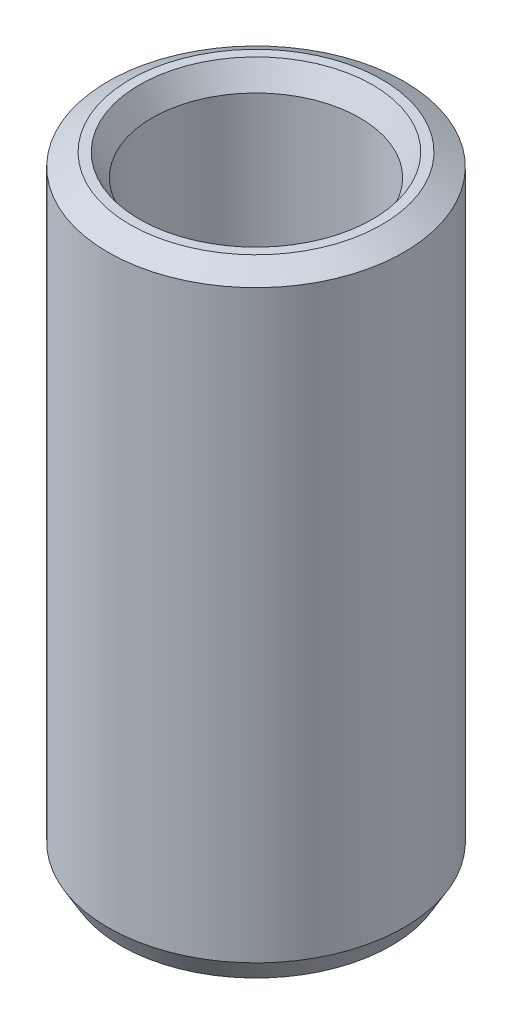
SolidWorks part; units mm, degrees
ref_plane "Front Plane" through (0, 0, 0) normal (0, 0, 1) x (1, 0, 0)
ref_plane "Top Plane" through (0, 0, 0) normal (0, 1, 0) x (1, 0, 0)
ref_plane "Right Plane" through (0, 0, 0) normal (1, 0, 0) x (0, 0, -1)
sketch "Sketch1" plane through (0, 0, 0) normal (0, 1, 0) x (1, 0, 0)
  circle A0 centre (0, 0) radius 32.5
  dimension "SLEEVE_OD" = 65
extrude "Boss-Extrude1" add sketch "Sketch1" along normal blind 136.0732
sketch "Sketch2" plane through (0, 0, 0) normal (0, 1, 0) x (1, 0, 0)
  circle A0 centre (0, 0) radius 22.7729
  dimension "BORE_D" = 45.5457
extrude "Cut-Extrude1" cut sketch "Sketch2" along normal through all
chamfer "Chamfer1" distance 2.81 angle 60 4 edges at (0, 136.0732, 22.7729) (0, 0, 22.7729) (0, 0, 32.5) (0, 136.0732, 32.5) first distance on face at (0, 136.0732, 22.7729) first distance on face at (0, 0, 22.7729) first distance on face at (0, 136.0732, 32.5)
